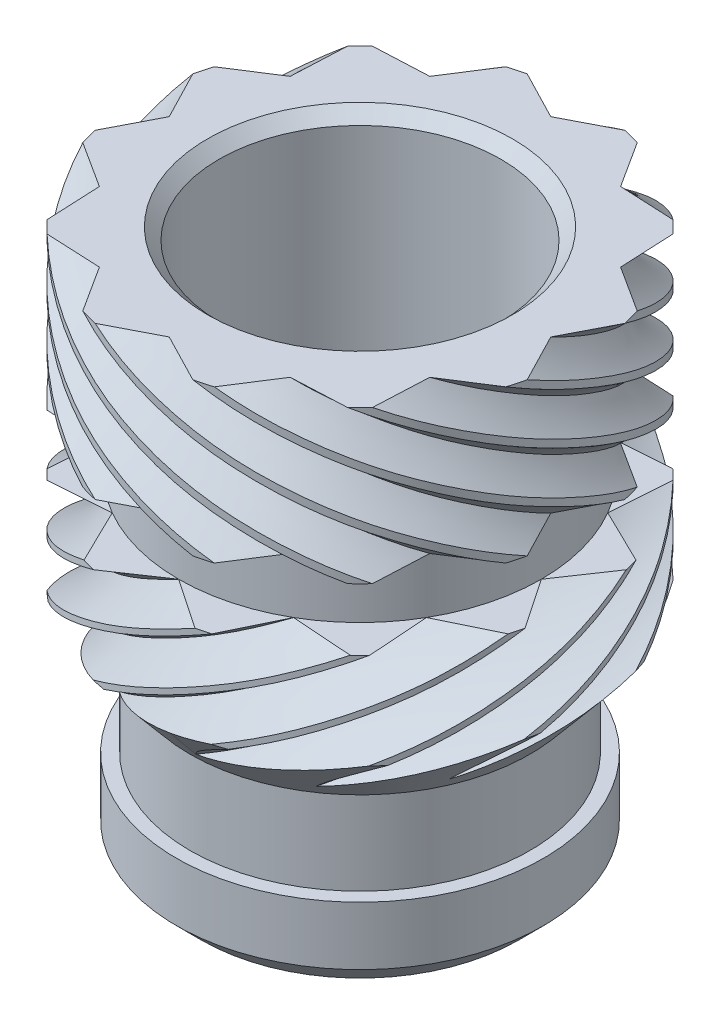
SolidWorks part; units mm, degrees
ref_plane "Front Plane" through (0, 0, 0) normal (0, 0, 1) x (1, 0, 0)
ref_plane "Top Plane" through (0, 0, 0) normal (0, 1, 0) x (1, 0, 0)
ref_plane "Right Plane" through (0, 0, 0) normal (1, 0, 0) x (0, 0, -1)
sketch "Sketch1" plane through (0, 0, 0) normal (0, 0, 1) x (1, 0, 0)
  line L0 (0, -2.87) -> (0, 2.87) construction
  line L1 (1.8115, -1.981) -> (1.955, -1.981) construction
  line L2 (1.955, -2.87) -> (0, -2.87) construction
  line L3 (2.36, 2.87) -> (2.36, 1.244) construction
  line L4 (2.36, 1.244) -> (1.933, 1.244) construction
  line L5 (1.933, 1.244) -> (1.933, 0.584) construction
  line L6 (1.933, 0.584) -> (2.36, 0.584) construction
  line L7 (2.36, 0.584) -> (2.36, -1.092) construction
  line L8 (2.36, -1.092) -> (1.8115, -1.092) construction
  line L9 (1.8115, -1.092) -> (1.8115, -1.981) construction
  line L10 (1.933, 0.914) -> (0, 0.914) construction
  line L11 (1.955, -1.981) -> (1.955, -2.87) construction
  line L12 (0, 0) -> (1.5, 0) construction
  line L14 (2.36, 2.87) -> (2.36, 1.244) construction
  line L15 (2.36, 2.87) -> (0, 2.87) construction
  line L16 (1.5, 2.87) -> (1.5, -2.87) construction
  point P19 (0, 2.37)
  dimension "Installed Length" = 5.74
  dimension "TOP OD" = 4.72
  dimension "BTM OD" = 3.91
  dimension "D5" = 1.626
  dimension "Thread OD" = 3
  dimension "Thread Pitch" = 0.5
  dimension "D1" = 3.623
  dimension "D2" = 0.889
  dimension "D3" = 0.66
  dimension "D4" = 1.676
  dimension "D6" = 3.866
sketch "Sketch3" plane through (0, 0, 0) normal (0, 0, 1) x (1, 0, 0)
  line L0 (1.5, 2.87) -> (2.36, 2.87)
  line L1 (2.36, 2.87) -> (2.36, 1.244)
  line L2 (2.36, 1.244) -> (1.933, 1.244)
  line L3 (1.933, 1.244) -> (1.933, 0.584)
  line L12 (1.933, 0.584) -> (2.36, 0.584)
  line L13 (2.36, 0.584) -> (2.36, -0.4383)
  line L14 (2.36, 0.584) -> (2.36, -1.092) construction
  line L15 (2.36, -0.4383) -> (1.8115, -1.092)
  line L17 (1.8115, -1.092) -> (1.8115, -1.981)
  line L18 (1.8115, -1.981) -> (1.955, -1.981)
  line L19 (1.955, -1.981) -> (1.955, -2.6033)
  line L20 (1.955, -1.981) -> (1.955, -2.87) construction
  line L21 (1.955, -2.6033) -> (1.6883, -2.87)
  line L22 (1.955, -2.87) -> (0, -2.87) construction
  line L23 (1.6883, -2.87) -> (1.5, -2.87)
  line L24 (1.5, -2.87) -> (1.5, 2.87)
  dimension "D1" = 45
  dimension "D2" = 0.2667
  dimension "D3" = 40
revolve "Revolve1" add sketch "Sketch3" angle 360 about L0
chamfer "Chamfer1" distance 0.125 angle 45 2 edges at (0, 2.87, -1.5) (0, -2.87, -1.5)
sketch "Sketch29" plane through (0, 0, 0) normal (0, 1, 0) x (1, 0, 0)
  circle A0 centre (0, 0) radius 1.5
  point P2 (0, -1.5)
sketch "Sketch8" [suppressed] plane through (0, 2.87, 0) normal (0, 1, 0) x (1, 0, 0)
  circle A1 centre (0, 0) radius 1.5
  point P1 (0, 1.5)
curve "Helix/Spiral2" [suppressed] pitch 0.5 height 6.24 turns 12.48
sketch "Sketch22" [suppressed] plane through (0, 0, 0) normal (0, 0, 1) x (1, 0, 0)
  line L0 (1.5541, 3.3388) -> (1.1211, 3.0888) construction
  line L1 (1.1211, 3.0888) -> (1.5541, 2.8388) construction
  line L2 (1.5541, 2.8388) -> (1.5541, 3.3388) construction
  line L3 (1.5, 3.3075) -> (1.5, 2.87) construction
  line L4 (1.5541, 3.0888) -> (1.5, 3.0888) construction
  line L5 (1.5, 3.0888) -> (1.1752, 3.0888) construction
  line L6 (1.1752, 3.0888) -> (1.1211, 3.0888) construction
  line L7 (1.1752, 3.12) -> (1.1752, 3.0575)
  line L8 (1.5271, 3.3231) -> (1.5271, 2.8544)
  line L9 (1.1752, 3.0575) -> (1.5271, 2.8544)
  line L10 (1.1752, 3.12) -> (1.5271, 3.3231)
  point P12 (1.5271, 3.0888)
  dimension "D1" = 0.5
  dimension "D2" = 0.0625
sweep "Sweep1" [suppressed] add profiles "Sketch22" path "Helix/Spiral2"
sketch "Sketch23" [suppressed] plane through (0, 2.87, 0) normal (0, 1, 0) x (1, 0, 0)
  circle A0 centre (0, 0) radius 1.625 construction
  circle A1 centre (0, 0) radius 1.625
extrude "Cut-Extrude15" [suppressed] cut sketch "Sketch23" against normal through all draft 45 and the other way through all
sketch "Sketch24" [suppressed] plane through (0, -2.87, 0) normal (0, -1, 0) x (1, 0, 0)
  circle A1 centre (0, 0) radius 1.625
  circle A2 centre (0, 0) radius 1.625
  dimension "D1" = 0
extrude "Cut-Extrude16" [suppressed] cut sketch "Sketch24" against normal through all draft 45 and the other way through all
sketch "Sketch25" plane through (0, 1.244, 0) normal (0, -1, 0) x (1, 0, 0)
  circle A0 centre (0, 0) radius 2.033
  circle A1 centre (0, 0) radius 2.36 construction
  circle A2 centre (0, 0) radius 1.933 construction
  circle A3 centre (0, 0) radius 1.933 construction
  dimension "D1" = 0.1
curve "Helix/Spiral3" pitch 6.504 height 1.626 radius 2.033 left hand yes centre (0, 1.244, 0) axis (0, 1, 0) start towards (0, 0, 1)
sketch "Sketch26" plane through (0, 1.244, 0) normal (0, -1, 0) x (1, 0, 0)
  line L0 (0, 2.033) -> (-0.6324, 2.36)
  line L1 (-0.6324, 2.36) -> (0.6324, 2.36)
  line L2 (0.6324, 2.36) -> (0, 2.033)
  line L3 (-0.6324, 2.36) -> (0, 0) construction
  line L4 (0, 0) -> (0.6324, 2.36) construction
  circle A0 centre (0, 0) radius 2.36 construction
  dimension "D1" = 30
sweep "Cut-Sweep1" cut profiles "Sketch26" path "Helix/Spiral3" align with end faces yes
sketch "Sketch27" plane through (0, 0.584, 0) normal (0, 1, 0) x (1, 0, 0)
  circle A0 centre (0, 0) radius 1.933 construction
  circle A1 centre (0, 0) radius 1.933
curve "Helix/Spiral4" pitch 6.504 height 1.676 radius 1.933 centre (0, 0.584, 0) axis (0, -1, 0) start towards (0, 0, 1)
sketch "Sketch28" plane through (0, 0.584, 0) normal (0, 1, 0) x (1, 0, 0)
  line L0 (0, -1.933) -> (-0.6324, -2.36)
  line L1 (-0.6324, -2.36) -> (0.6324, -2.36)
  line L2 (0.6324, -2.36) -> (0, -1.933)
  line L3 (-0.6324, -2.36) -> (0, 0) construction
  line L4 (0, 0) -> (0.6324, -2.36) construction
  circle A0 centre (0, 0) radius 2.36 construction
  dimension "D1" = 30
sweep "Cut-Sweep3" cut profiles "Sketch28" path "Helix/Spiral4" align with end faces yes
pattern_circular "CirPattern1" count 12 over 360 about axis through (0, -2.87, 0) along (0, 1, 0) of "Cut-Sweep1", "Cut-Sweep3" reverse direction yes
equation "\"D3@Helix/Spiral2\" = \"Installed Length@Sketch1\" + \"Thread Pitch@Sketch1\""
equation "\"D4@Helix/Spiral2\" = \"Thread Pitch@Sketch1\""
equation "\"D2@Sketch3\"=\"D2@Sketch1\"*0.3"
equation "\"D1@Chamfer1\"=\"Thread Pitch@Sketch1\"*0.25"
equation "\"D2@Sketch22\"=\"D1@Sketch22\"/8"
equation "\"D1@Sketch22\" = \"Thread Pitch@Sketch1\""
equation "\"D3@Helix/Spiral3\"=\"D5@Sketch1\""
equation "\"D4@Helix/Spiral3\"=\"D5@Sketch1\"*4"
equation "\"D3@Helix/Spiral4\"=\"D4@Sketch1\""
equation "\"D4@Helix/Spiral4\"=\"D4@Helix/Spiral3\""
